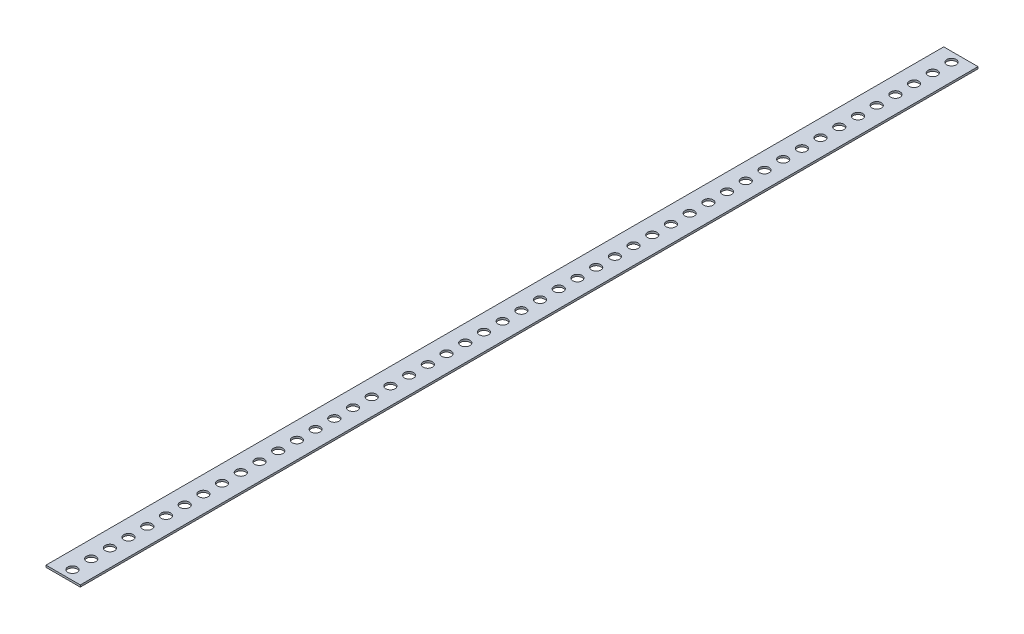
SolidWorks part; units mm, degrees
ref_plane "Front Plane" through (0, 0, 0) normal (0, 0, 1) x (1, 0, 0)
ref_plane "Top Plane" through (0, 0, 0) normal (0, 1, 0) x (1, 0, 0)
ref_plane "Right Plane" through (0, 0, 0) normal (1, 0, 0) x (0, 0, -1)
sketch "Sketch1" plane through (0, 0, 0) normal (0, 1, 0) x (1, 0, 0)
  line L1 (-17.4625, 457.2) -> (17.4625, 457.2) construction
  line L2 (-17.4625, 457.2) -> (-17.4625, -457.2) construction
  line L3 (-17.4625, -457.2) -> (17.4625, -457.2) construction
  line L4 (17.4625, 457.2) -> (17.4625, -457.2) construction
  line L5 (-17.4625, 457.2) -> (17.4625, -457.2) construction
  line L6 (-17.4625, -457.2) -> (17.4625, 457.2) construction
  line L8 (0, -457.2) -> (0, -447.675) construction
  circle A0 centre (0, -447.675) radius 4.7625 construction
  circle A2 centre (0, -428.625) radius 4.7625 construction
  point P0 (0, 0)
  point P13 (0, -387.35)
  point P19 (0, 387.35)
  dimension "D1" = 9.525
  dimension "Length" = 914.4
  dimension "Width (A)" = 34.925
  dimension "D3" = 19.05
  dimension "D4" = 9.525
  dimension "D5" = 69.85
  dimension "D6" = 69.85
sketch "Sketch2" plane through (0, 0, 0) normal (1, 0, 0) x (0, 0, -1)
  line L0 (0, -0.9919) -> (0, 0.9919) construction
  dimension "Thickness" = 1.9837
sketch "Sketch3" plane through (0, 0, 0) normal (0, 1, 0) x (1, 0, 0)
  line L0 (-17.4625, 457.2) -> (17.4625, 457.2) construction
  line L1 (17.4625, 457.2) -> (17.4625, -457.2) construction
  line L2 (-17.4625, -457.2) -> (17.4625, -457.2) construction
  line L3 (-17.4625, 457.2) -> (-17.4625, -457.2) construction
  line L4 (-17.4625, 457.2) -> (17.4625, 457.2)
  line L5 (17.4625, 457.2) -> (17.4625, -457.2)
  line L6 (-17.4625, -457.2) -> (17.4625, -457.2)
  line L7 (-17.4625, 457.2) -> (-17.4625, -457.2)
extrude "Boss-Extrude1" add sketch "Sketch3" against normal up to vertex (0.9919 mm away) and the other way up to vertex (0.9919 mm away) up to point (0, -0.9919, 0) other way up to point (0, 0.9919, 0)
sketch "Sketch4" plane through (0, 0.9919, 0) normal (0, 1, 0) x (1, 0, 0)
  circle A0 centre (0, -447.675) radius 4.7625 construction
  circle A1 centre (0, -447.675) radius 4.7625
extrude "Cut-Extrude1" cut sketch "Sketch4" against normal up to next
pattern_linear "LPattern1" count 53 spacing 19.05 along (0, 0, -1) of "Cut-Extrude1"
equation "\"D4@Sketch1\"=\"D3@Sketch1\"/2"
equation "\"D3@Sketch1\"=\"D1@Sketch1\"*2"
equation "\"D3@LPattern1\"=\"D3@Sketch1\""
equation "\"D1@LPattern1\"=( \"Length@Sketch1\" / \"D3@Sketch1\" ) + 5"
equation "\"D5@Sketch1\"=\"Width (A)@Sketch1\"*2"
equation "\"D6@Sketch1\"=\"D5@Sketch1\""
